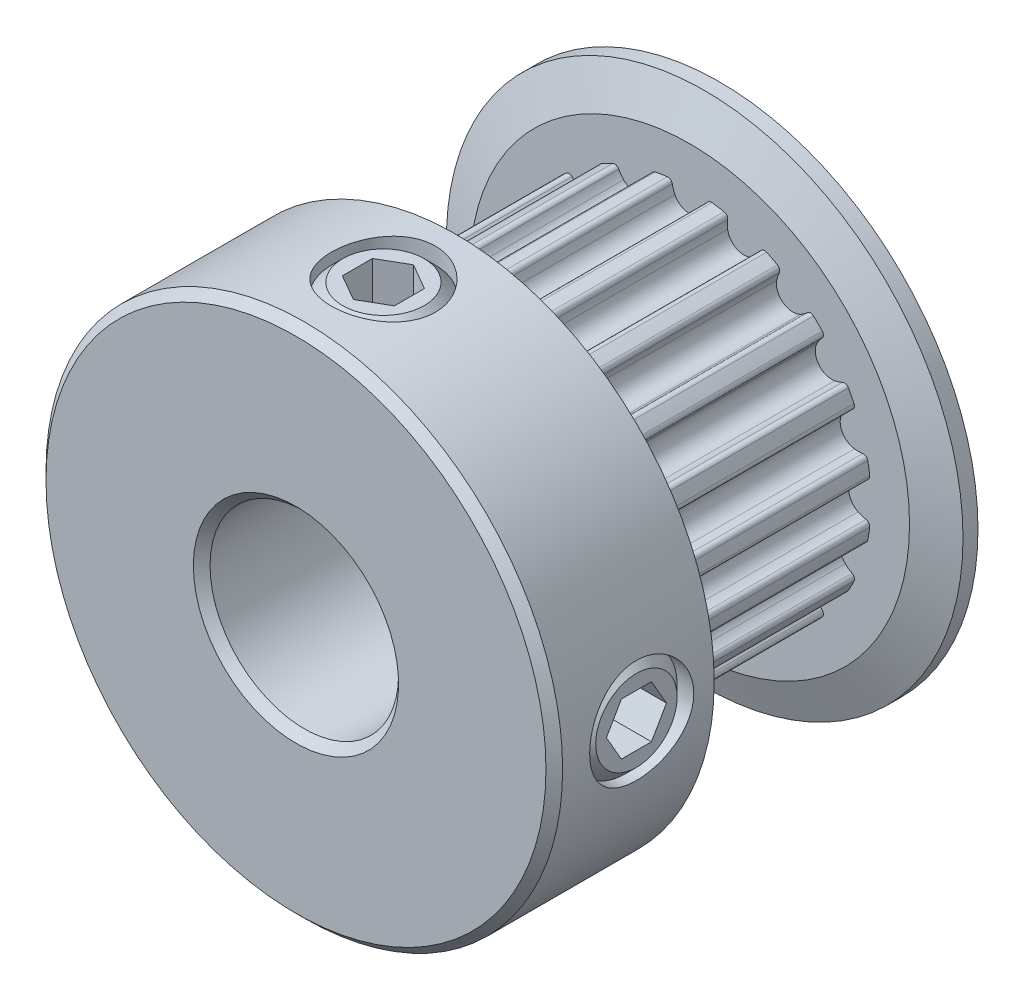
SolidWorks part; units mm, degrees
note: '?' marks a value the reader was unsure of.
ref_plane "Front Plane" through (0, 0, 0) normal (0, 0, 1) x (1, 0, 0)
ref_plane "Top Plane" through (0, 0, 0) normal (0, 1, 0) x (1, 0, 0)
ref_plane "Right Plane" through (0, 0, 0) normal (1, 0, 0) x (0, 0, -1)
sketch "Sketch1" plane through (0, 0, 0) normal (0, 0, 1) x (1, 0, 0)
  line L1 (-1.7499, 5.3585) -> (1.7499, 5.3585) construction
  line L4 (0, 0) -> (0, 5.3585) construction
  line L5 (0, 5.3585) -> (0, 11.2111) construction
  line L6 (0, 6.3625) -> (1.9751, 6.0482) construction
  line L7 (1.9751, 6.0482) -> (2.6648, 5.8229) construction
  line L8 (1.9751, 6.0482) -> (1.7499, 5.3585) construction
  line L9 (-1.9751, 6.0482) -> (-1.7499, 5.3585) construction
  line L10 (-1.8963, 5.8067) -> (-2.841, 8.6995)
  line L11 (-2.841, 8.6995) -> (2.841, 8.6995)
  line L12 (2.841, 8.6995) -> (1.8963, 5.8067)
  circle A0 centre (0, 0) radius 6.3625 construction
  circle A1 centre (0, 0) radius 8.6995 construction
  circle A2 centre (0, 0) radius 6.1085 construction
  arc A3 (-0.4989, 5.6703) -> (0.4989, 5.6703) centre (0, 5.9135) ccw
  arc A4 (-0.4989, 5.6703) -> (-0.5855, 5.9387) centre (0.4, 6.1085) cw
  arc A5 (-1.8963, 5.8067) -> (-0.7518, 6.0621) centre (0, 0) cw
  arc A6 (-0.5855, 5.9387) -> (-0.7518, 6.0621) centre (-0.7333, 5.9132) ccw
  arc A7 (1.8963, 5.8067) -> (0.7518, 6.0621) centre (0, 0) ccw
  arc A8 (0.5855, 5.9387) -> (0.7518, 6.0621) centre (0.7333, 5.9132) cw
  arc A9 (0.4989, 5.6703) -> (0.5855, 5.9387) centre (-0.4, 6.1085) ccw
  point P6 (0, 20.9083)
  point P11 (0, 6.3625)
  point P13 (0, 8.6995)
  point P14 (0, 6.1085)
  dimension "D1" = 9.6972
  dimension "D2" = 4.8486
sketch "Sketch2" plane through (0, 0, 0) normal (1, 0, 0) x (0, 0, -1)
  line L0 (-7.135, 3.175) -> (7.135, 3.175)
  line L1 (-7.135, 3.175) -> (-7.135, 8.6995)
  line L2 (-1.75, 8.6995) -> (-7.135, 8.6995)
  line L3 (-2.255, 3.175) -> (-2.255, 8.6995) construction
  line L4 (-2.255, 8.6995) -> (-1.245, 8.6995) construction
  line L5 (-1.245, 8.6995) -> (-1.245, 6.1085) construction
  line L6 (-1.245, 6.1085) -> (6.125, 6.1085)
  line L7 (6.125, 6.1085) -> (6.125, 8.6995) construction
  line L8 (6.125, 8.6995) -> (7.135, 8.6995) construction
  line L9 (7.135, 8.6995) -> (7.135, 3.175)
  line L10 (-7.135, 0) -> (7.135, 0) construction
  line L11 (6.63, 8.6995) -> (6.125, 7.404)
  line L12 (-1.245, 7.404) -> (-1.75, 8.6995)
  line L14 (-1.245, 7.404) -> (-1.245, 6.1085)
  line L15 (6.125, 6.1085) -> (6.125, 7.404)
  line L16 (6.63, 8.6995) -> (7.135, 8.6995)
  arc A0 (-1.245, 7.404) -> (-1.75, 8.6995) centre (-3.1592, 7.404) ccw construction
  arc A1 (6.125, 7.404) -> (6.63, 8.6995) centre (8.0392, 7.404) cw construction
  point P12 (-1.245, 7.404)
  point P14 (-1.75, 8.6995)
  point P20 (6.125, 7.404)
  point P21 (6.63, 8.6995)
  point P25 (6.125, 0)
  point P26 (-1.245, 0)
  dimension "OA" = 14.27
  dimension "Bore" = 6.35
  dimension "Outside Width" = 8.38
  dimension "Inside Width" = 7.37
revolve "Revolve1" add sketch "Sketch2" angle 360 mid plane about L10
sketch "Sketch3" plane through (0, 0, 0) normal (0, 0, 1) x (1, 0, 0)
  line L6 (2.841, 8.6995) -> (-2.841, 8.6995)
  line L7 (1.8963, 5.8067) -> (2.841, 8.6995)
  line L8 (-2.841, 8.6995) -> (-1.8963, 5.8067)
  line L9 (2.841, 8.6995) -> (-2.841, 8.6995)
  line L10 (1.8963, 5.8067) -> (2.841, 8.6995)
  line L11 (-2.841, 8.6995) -> (-1.8963, 5.8067)
  arc A8 (1.8963, 5.8067) -> (0.7518, 6.0621) centre (0, 0) ccw
  arc A9 (0.7518, 6.0621) -> (0.5855, 5.9387) centre (0.7333, 5.9132) ccw
  arc A10 (0.4989, 5.6703) -> (0.5855, 5.9387) centre (-0.4, 6.1085) ccw
  arc A11 (-0.4989, 5.6703) -> (0.4989, 5.6703) centre (0, 5.9135) ccw
  arc A12 (-0.5855, 5.9387) -> (-0.4989, 5.6703) centre (0.4, 6.1085) ccw
  arc A13 (-0.5855, 5.9387) -> (-0.7518, 6.0621) centre (-0.7333, 5.9132) ccw
  arc A14 (-0.7518, 6.0621) -> (-1.8963, 5.8067) centre (0, 0) ccw
  arc A15 (1.8963, 5.8067) -> (0.7518, 6.0621) centre (0, 0) ccw
  arc A16 (0.7518, 6.0621) -> (0.5855, 5.9387) centre (0.7333, 5.9132) ccw
  arc A17 (0.4989, 5.6703) -> (0.5855, 5.9387) centre (-0.4, 6.1085) ccw
  arc A18 (-0.4989, 5.6703) -> (0.4989, 5.6703) centre (0, 5.9135) ccw
  arc A19 (-0.5855, 5.9387) -> (-0.4989, 5.6703) centre (0.4, 6.1085) ccw
  arc A20 (-0.5855, 5.9387) -> (-0.7518, 6.0621) centre (-0.7333, 5.9132) ccw
  arc A21 (-0.7518, 6.0621) -> (-1.8963, 5.8067) centre (0, 0) ccw
  dimension "D1" = 0
extrude "Cut-Extrude1" cut sketch "Sketch3" against normal up to vertex (6.125 mm away) from vertex at 1.245 starting at point (0, 6.1085, 1.245)
pattern_circular "CirPattern1" count 20 over 360 about axis through (0, 0, 0) along (0, 0, 1) of "Cut-Extrude1"
sketch "Sketch4" plane through (0, 0, 0) normal (1, 0, 0) x (0, -1, 0)
  line L0 (0, -1.245) -> (0, -7.135) construction
  line L1 (-3.175, -7.135) -> (3.175, -7.135) construction
  line L2 (7.404, -1.245) -> (-7.404, -1.245) construction
  circle A0 centre (0, -4.19) radius 1.7526
extrude "Cut-Extrude2" cut sketch "Sketch4" along normal through all
ref_plane "Plane1" through (0, 0, 4.19) normal (0, 0, 1) x (1, 0, 0)
sketch "Sketch5" plane through (0, 0, 4.19) normal (0, 0, 1) x (1, 0, 0)
  line L0 (0, 0) -> (0, 8.6995) construction
  line L1 (3.175, -1.3716) -> (3.175, 0)
  line L2 (3.556, -1.7526) -> (8.1401, -1.7526)
  line L3 (3.175, 0) -> (8.6995, 0) construction
  line L4 (3.175, 0) -> (8.5211, 0)
  line L5 (8.5211, 0) -> (8.5211, -1.3716)
  line L6 (3.556, -1.7526) -> (3.175, -1.3716)
  line L7 (8.5211, -1.3716) -> (8.1401, -1.7526)
  circle A0 centre (0, 0) radius 8.6995 construction
  circle A1 centre (0, 0) radius 3.175 construction
  point P2 (3.175, -1.7526)
  point P11 (8.5211, -1.7526)
revolve "Revolve2" add sketch "Sketch5" angle 360 mid plane about L4
sketch "Sketch6" plane through (8.5211, 5.3841, 0) normal (-1, 0, 0) x (0, -1, 0)
  line L1 (5.3841, 5.2019) -> (4.5078, 4.6959)
  line L2 (4.5078, 4.6959) -> (4.5078, 3.6841)
  line L3 (4.5078, 3.6841) -> (5.3841, 3.1781)
  line L4 (5.3841, 3.1781) -> (6.2604, 3.6841)
  line L5 (6.2604, 3.6841) -> (6.2604, 4.6959)
  line L6 (6.2604, 4.6959) -> (5.3841, 5.2019)
  circle A0 centre (5.3841, 4.19) radius 0.8763 construction
  dimension "D1" = 1.7526
extrude "Cut-Extrude3" cut sketch "Sketch6" along normal blind 1.3144
pattern_circular "CirPattern3" count 2 over 90 about axis through (0, 0, 0) along (0, 0, 1) of "Cut-Extrude2", "Revolve2", "Cut-Extrude3"
chamfer "Chamfer1" distance 0.2807 angle 45 2 edges at (3.175, 0, 7.135) (8.6995, 0, 7.135)
ref_axis "Center Axis 1" through (0, 0, -7.135) along (0, 0, 1)?
ref_plane "Contact Plane 1" through (0, 0, 7.135) normal (0, 0, 1) x (1, 0, 0)
ref_plane "Contact Plane 2" through (0, 0, -7.135) normal (0, 0, -1) x (-1, 0, 0)
equation "\"D2@Sketch1\"= \"D1@Sketch1\" / 2"
equation "\"D1@Sketch6\" = \"Set Screw@Sketch4\" / 2"
equation "\"D1@Cut-Extrude3\" = \"D1@Sketch6\"*.75"
